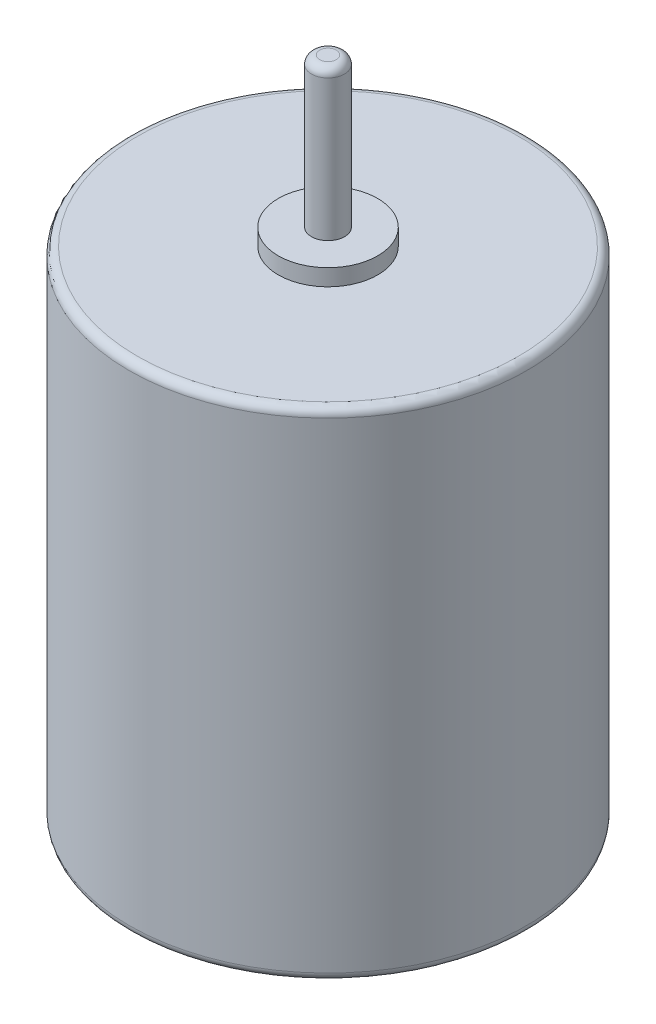
SolidWorks part; units mm, degrees
ref_plane "Front Plane" through (0, 0, 0) normal (0, 0, 1) x (1, 0, 0)
ref_plane "Top Plane" through (0, 0, 0) normal (0, 1, 0) x (1, 0, 0)
ref_plane "Right Plane" through (0, 0, 0) normal (1, 0, 0) x (0, 0, -1)
sketch "Sketch1" plane through (0, 0, 0) normal (0, 1, 0) x (1, 0, 0)
  circle A0 centre (0, 0) radius 12
  dimension "D1" = 24
extrude "Motor housing" add sketch "Sketch1" along normal blind 30
sketch "Sketch2" plane through (0, 30, 0) normal (0, 1, 0) x (1, 0, 0)
  circle A0 centre (0, 0) radius 3
  dimension "D1" = 6
extrude "Motor front nipple" add sketch "Sketch2" along normal blind 1
sketch "Sketch4" plane through (0, 31, 0) normal (0, 1, 0) x (1, 0, 0)
  circle A0 centre (0, 0) radius 1
  dimension "D1" = 2
extrude "Front axle" add sketch "Sketch4" along normal blind 9
fillet "Fillet1" radius 0.5 1 edges at (0, 40, 1)
fillet "Fillet2" radius 0.5 2 edges at (0, 0, 12) (0, 30, 12)
